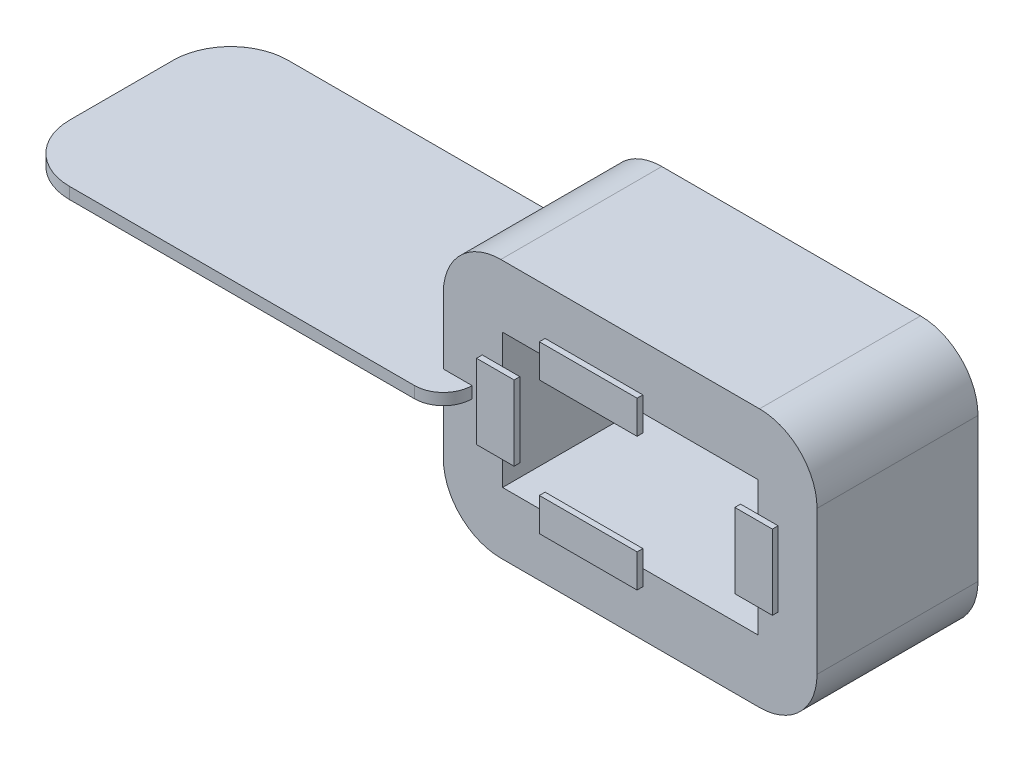
SolidWorks part; units mm, degrees
ref_plane "前基準面" through (0, 0, 0) normal (0, 0, 1) x (1, 0, 0)
ref_plane "上基準面" through (0, 0, 0) normal (0, 1, 0) x (1, 0, 0)
ref_plane "右基準面" through (0, 0, 0) normal (1, 0, 0) x (0, 0, -1)
sketch "草圖1" plane through (0, 0, 0) normal (0, 0, 1) x (1, 0, 0)
  line L0 (-9.02, 0) -> (7.9922, 0) construction
  line L2 (-59.9347, 22.5) -> (5.0653, 22.5)
  line L3 (-59.9347, 22.5) -> (-59.9347, -22.5)
  line L4 (-59.9347, -22.5) -> (5.0653, -22.5)
  line L5 (5.0653, 22.5) -> (5.0653, -22.5)
  dimension "D1" = 45
  dimension "D2" = 22.5
  dimension "D3" = 65
extrude "填料-伸長1" add sketch "草圖1" along normal blind 28
sketch "草圖2" plane through (0, 0, 0) normal (0, 0, 1) x (1, 0, 0)
  line L0 (-59.9347, 0) -> (5.361, 0) construction
  line L1 (-59.9347, 22.5) -> (-59.9347, -22.5) construction
  line L2 (-27.4347, 22.5) -> (-27.4347, -22.5) construction
  line L3 (5.0653, 22.5) -> (-59.9347, 22.5) construction
  line L4 (-59.9347, -22.5) -> (5.0653, -22.5) construction
  line L6 (-49.6347, 11.7) -> (-5.2347, 11.7)
  line L7 (-49.6347, 11.7) -> (-49.6347, -11.7)
  line L8 (-49.6347, -11.7) -> (-5.2347, -11.7)
  line L9 (-5.2347, 11.7) -> (-5.2347, -11.7)
  dimension "D1" = 44.4
  dimension "D2" = 23.4
  dimension "D3" = 10.3
  dimension "D4" = 10.8
extrude "除料-伸長1" cut sketch "草圖2" along normal blind 39
ref_plane "平面1" through (0, 0, 28) normal (0, 0, 1) x (1, 0, 0)
sketch "草圖3" plane through (0, 0, 28) normal (0, 0, 1) x (1, 0, 0)
  line L0 (-59.9347, 22.5) -> (-59.9347, -22.5) construction
  line L2 (-59.9347, 12) -> (-55.9347, 12)
  line L3 (-59.9347, 12) -> (-59.9347, -12)
  line L4 (-59.9347, -12) -> (-55.9347, -12)
  line L5 (-55.9347, 12) -> (-55.9347, -12)
  line L8 (-5.2347, -11.7) -> (-49.6347, -11.7) construction
  dimension "D1" = 4
  dimension "D2" = 24
  dimension "D3" = 0.3
ref_plane "平面2" through (-59.9347, 0, 0) normal (-1, 0, 0) x (0, 0, 1)
sketch "草圖6" plane through (0, 0, 28) normal (0, 0, 1) x (1, 0, 0)
  line L0 (-15.2347, 0.3) -> (5.0653, -22.5)
  line L1 (-5.2347, 11.7) -> (-5.2347, -11.7) construction
  line L2 (-5.2347, -11.7) -> (-49.6347, -11.7) construction
  line L3 (-15.2347, 0.3) -> (-15.2347, -22.5)
  line L4 (-59.9347, -22.5) -> (5.0653, -22.5) construction
  line L5 (-15.2347, -22.5) -> (5.0653, -22.5)
  dimension "D1" = 10
  dimension "D2" = 12
ref_plane "平面4" through (0, 0, 0) normal (0, 0, -1) x (-1, 0, 0)
fillet "圓角1" radius 10 1 edges at (-59.9347, -22.5, 14) type face fillet first side face at (-59.9347, 0, 14) second side face at (-27.4347, -22.5, 14)
fillet "圓角2" radius 10 1 edges at (-59.9347, 22.5, 14) type face fillet first side face at (-27.4347, 22.5, 14) second side face at (-59.9347, 5, 14)
fillet "圓角3" radius 10 1 edges at (5.0653, 22.5, 14) type face fillet first side face at (-22.4347, 22.5, 14) second side face at (5.0653, 0, 14)
fillet "圓角4" radius 10 1 edges at (5.0653, -22.5, 14) type face fillet first side face at (-22.4347, -22.5, 14) second side face at (5.0653, -5, 14)
ref_plane "平面6" through (0, 0, 29) normal (0, 0, 1) x (1, 0, 0)
sketch "草圖10" plane through (0, 0, 29) normal (0, 0, 1) x (1, 0, 0)
  line L6 (-49.6347, 0) -> (-4.2092, 0) construction
  line L7 (-49.6347, -11.7) -> (-49.6347, 11.7) construction
  line L8 (-27.4347, -11.7) -> (-27.4347, 19.297) construction
  line L9 (-5.2347, -11.7) -> (-49.6347, -11.7) construction
  line L11 (-49.6347, 6.5) -> (-53.1651, 6.5)
  line L14 (-53.1651, 6.5) -> (-53.1651, -6.5)
  line L17 (-49.6347, 6.5) -> (-46.6347, 6.5)
  line L18 (-46.6347, 6.5) -> (-46.6347, -6.5)
  line L20 (-42.2347, -11.7) -> (-42.2347, -8.7)
  line L25 (-42.2347, -11.7) -> (-42.2347, -14.4546)
  line L27 (-8.2347, 6.5) -> (-8.2347, -6.5)
  line L28 (-8.2347, -6.5) -> (-5.2347, -6.5)
  line L29 (-5.2347, -6.5) -> (-1.7043, -6.5)
  line L30 (-1.7043, 6.5) -> (-1.7043, -6.5)
  line L32 (-25.2347, 8.7) -> (-25.2347, 14.4546)
  line L33 (-25.2347, -14.4546) -> (-25.2347, -8.7)
  line L34 (-25.2347, -14.4546) -> (-42.2347, -14.4546)
  line L35 (-25.2347, -8.7) -> (-42.2347, -8.7)
  line L36 (-25.2347, 8.7) -> (-42.2347, 8.7)
  line L37 (-25.2347, 14.4546) -> (-42.2347, 14.4546)
  line L38 (-42.2347, 8.7) -> (-42.2347, 14.4546)
  line L39 (-46.6347, -6.5) -> (-53.1651, -6.5)
  line L40 (-1.7043, 6.5) -> (-8.2347, 6.5)
  dimension "D3" = 13
  dimension "D4" = 6.5
extrude "填料-伸長6" add sketch "草圖10" against normal blind 1 separate body
sketch "草圖19" plane through (0, 0, 0) normal (0, 1, 0) x (1, 0, 0)
  line L0 (-59.9347, 6.325) -> (-59.9347, -6.325) construction
  line L1 (-59.9347, 1.0971) -> (-54.9347, 1.0971)
  line L2 (-59.9347, 1.0971) -> (-59.9347, -29)
  line L3 (-59.9347, -29) -> (-54.9347, -29)
  line L4 (-54.9347, 1.0971) -> (-54.9347, -29)
  line L5 (-24.75, -29) -> (24.75, -29) construction
  dimension "D1" = 5
ref_plane "平面7" through (0, 0, 28) normal (0, 0, 1) x (1, 0, 0)
sketch "草圖20" plane through (0, 0, 28) normal (0, 0, 1) x (1, 0, 0)
  line L0 (-59.9347, 12.5) -> (-59.9347, -12.5) construction
  line L1 (-59.9347, 1) -> (-54.932, 1)
  line L2 (-59.9347, 1) -> (-59.9347, -1)
  line L3 (-59.9347, -1) -> (-54.932, -1)
  line L4 (-54.932, 1) -> (-54.932, -1)
  line L5 (-59.9347, 0) -> (-54.9347, 0) construction
  dimension "D1" = 5.0026
  dimension "D2" = 2
  dimension "D3" = 1
extrude "填料-伸長7" add sketch "草圖20" along normal blind 5
ref_plane "平面8" through (0, 0, 0) normal (0, 0, -1) x (-1, 0, 0)
sketch "草圖21" plane through (0, 0, 0) normal (0, 0, -1) x (-1, 0, 0)
  line L0 (59.9347, 0) -> (54.9347, 0) construction
  line L1 (54.9323, 1) -> (59.9347, 1)
  line L2 (54.9323, 1) -> (54.9323, -1)
  line L3 (54.9323, -1) -> (59.9347, -1)
  line L4 (59.9347, 1) -> (59.9347, -1)
  dimension "D1" = 5.0023
  dimension "D2" = 2
  dimension "D3" = 1
extrude "填料-伸長8" add sketch "草圖21" along normal blind 5
sketch "草圖22" plane through (0, 0, 0) normal (0, 1, 0) x (1, 0, 0)
  line L2 (-59.9347, -14) -> (-129.9347, -14) construction
  line L4 (-59.9347, 5) -> (-129.9347, 5)
  line L5 (-59.9347, 5) -> (-59.9347, -33)
  line L6 (-59.9347, -33) -> (-129.9347, -33)
  line L7 (-129.9347, 5) -> (-129.9347, -33)
  dimension "D1" = 70
extrude "填料-伸長9" add sketch "草圖22" along normal blind 1 and the other way blind 1
fillet "圓角5" radius 5 1 edges at (-54.9323, 0, -5) type face fillet first side face at (-92.4335, 0, -5) second side face at (-54.9323, 0, -2.5)
fillet "圓角6" radius 5 1 edges at (-54.932, 0, 33) type face fillet first side face at (-92.4333, 0, 33) second side face at (-54.932, 0, 30.5)
fillet "圓角7" radius 10 1 edges at (-129.9347, 0, -5) type face fillet first side face at (-129.9347, 0, 14) second side face at (-94.9335, 0, -5)
fillet "圓角8" radius 10 1 edges at (-129.9347, 0, 33) type face fillet first side face at (-129.9347, 0, 19) second side face at (-94.9333, 0, 33)
